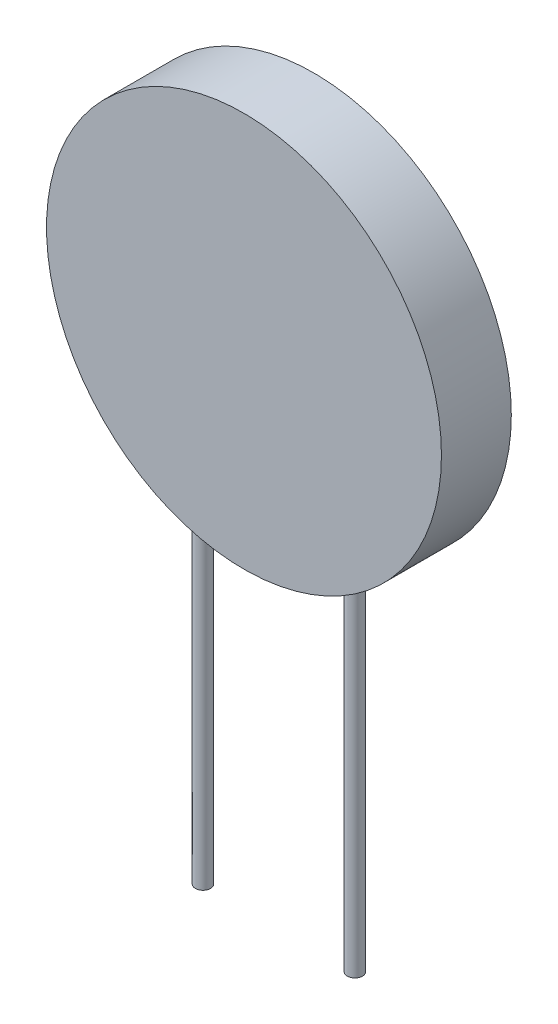
SolidWorks part; units mm, degrees
ref_plane "Front" through (0, 0, 0) normal (0, 0, 1) x (1, 0, 0)
ref_plane "Top" through (0, 0, 0) normal (0, 1, 0) x (1, 0, 0)
ref_plane "Right" through (0, 0, 0) normal (1, 0, 0) x (0, 0, -1)
sketch "Sketch1" plane through (0, 0, 0) normal (0, 0, 1) x (1, 0, 0)
  circle A0 centre (0, 0) radius 13
  dimension "D1" = 26
extrude "Boss-Extrude1" add sketch "Sketch1" along normal mid plane 4.6
sketch "Sketch2" plane through (0, 0, 0) normal (0, 1, 0) x (1, 0, 0)
  line L0 (-5, 0) -> (5, 0) construction
  circle A0 centre (-5, 0) radius 0.5
  circle A1 centre (5, 0) radius 0.5
  dimension "D2" = 1
  dimension "D1" = 10
extrude "Boss-Extrude2" add sketch "Sketch2" against normal blind 34.6
